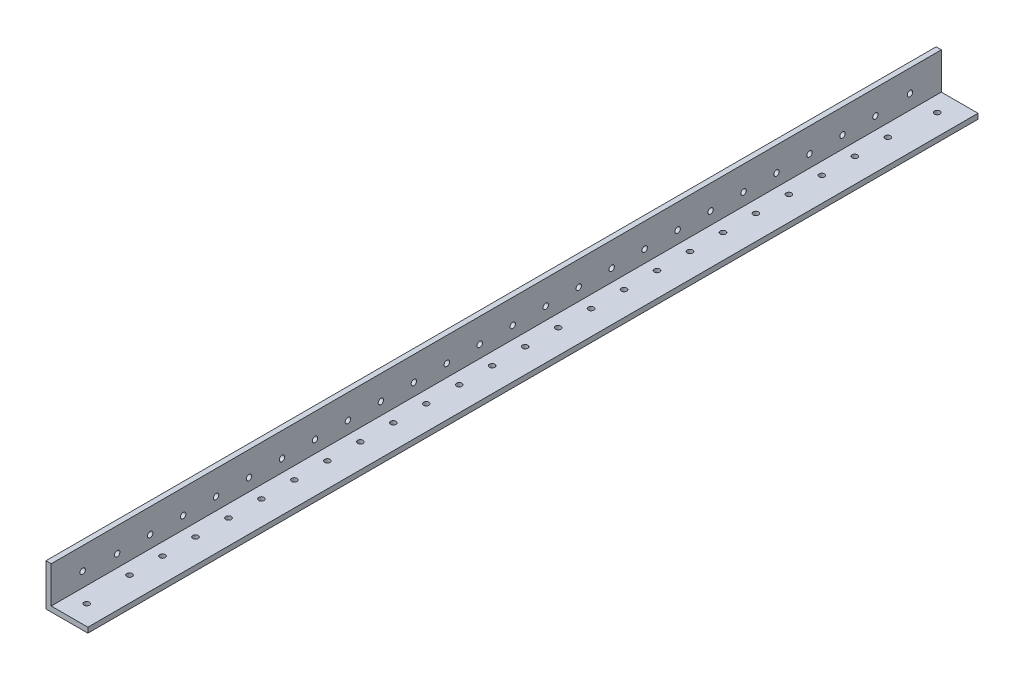
SolidWorks part; units mm, degrees
ref_plane "Front Plane" through (0, 0, 0) normal (0, 0, 1) x (1, 0, 0)
ref_plane "Top Plane" through (0, 0, 0) normal (0, 1, 0) x (1, 0, 0)
ref_plane "Right Plane" through (0, 0, 0) normal (1, 0, 0) x (0, 0, -1)
sketch "Sketch1" plane through (0, 0, 0) normal (0, 0, 1) x (1, 0, 0)
  line L0 (0, 25.4) -> (0, 0) construction
  line L1 (0, 0) -> (25.4, 0) construction
  line L2 (25.4, 0) -> (25.4, 3.175) construction
  line L3 (25.4, 3.175) -> (3.175, 3.175) construction
  line L4 (3.175, 3.175) -> (3.175, 25.4) construction
  line L6 (3.175, 25.4) -> (0, 25.4) construction
  arc A0 (3.175, 3.5814) -> (3.5814, 3.175) centre (3.5814, 3.5814) ccw construction
  point P4 (0, 0)
  dimension "Inside Corner Radius" = 0.4064
  dimension "Outside Height" = 25.4
  dimension "Inside Height" = 22.225
  dimension "Outside Width" = 25.4
  dimension "Inside Width" = 22.225
  dimension "Wall Thickness" = 3.175
  dimension "Shape" = 90
sketch "Sketch2" plane through (0, 0, 0) normal (1, 0, 0) x (0, 0, -1)
  line L0 (1219.2, 0) -> (-1219.2, 0) construction
  line L1 (-1219.2, 25.4) -> (-1219.2, 0) construction
  line L2 (1219.2, 25.4) -> (1219.2, 0) construction
  point P0 (-1189.99, 0)
  point P4 (0, 0)
  point P6 (1189.99, 0)
  dimension "D1" = 29.21
  dimension "D2" = 29.21
  dimension "D3" = 25.4
  dimension "Length" = 2438.4
sketch "Sketch3" plane through (0, 0, 0) normal (0, 0, 1) x (1, 0, 0)
  line L0 (3.175, 25.4) -> (0, 25.4)
  line L1 (0, 25.4) -> (0, 0)
  line L2 (0, 0) -> (25.4, 0)
  line L3 (25.4, 0) -> (25.4, 3.175)
  line L4 (25.4, 3.175) -> (3.175, 3.175)
  line L5 (3.175, 3.175) -> (3.175, 25.4)
extrude "Boss-Extrude1" add sketch "Sketch3" along normal mid plane 2438.4
fillet "Fillet1" radius 0.4064 1 edges at (3.175, 3.175, 0)
sketch "Sketch4" plane through (0, 0, 0) normal (-1, 0, 0) x (0, 0, 1)
  line L0 (1219.2, 25.4) -> (1219.2, 0) construction
  line L1 (-1219.2, 25.4) -> (679.2, 25.4)
  line L2 (-1219.2, 25.4) -> (-1219.2, -77.8785)
  line L3 (-1219.2, -77.8785) -> (679.2, -77.8785)
  line L4 (679.2, 25.4) -> (679.2, -77.8785)
  dimension "D1" = 540
extrude "Cut-Extrude1" cut sketch "Sketch4" against normal blind 60
sketch "Sketch5" plane through (0, 0, 679.2) normal (0, 0, -1) x (-1, 0, 0)
  line L0 (-3.175, 3.5814) -> (-3.175, 25.4) construction
  line L1 (-3.175, 6.1219) -> (-5.652, 6.1219)
  line L2 (-3.175, 6.1219) -> (-3.175, 3.175)
  line L3 (-3.175, 3.175) -> (-5.652, 3.175)
  line L4 (-5.652, 6.1219) -> (-5.652, 3.175)
  line L5 (-25.4, 3.175) -> (-3.5814, 3.175) construction
extrude "Cut-Extrude2" cut sketch "Sketch5" against normal blind 600
sketch "Sketch8" plane through (3.175, 0, 0) normal (1, 0, 0) x (0, 0, -1)
  line L0 (-1219.2, 3.175) -> (-1219.2, 25.4) construction
  line L1 (-1219.2, 3.175) -> (-679.2, 3.175) construction
  line L2 (-679.2, 3.175) -> (-679.2, 25.4) construction
  circle A0 centre (-1179.2, 10.675) radius 1.65
  circle A1 centre (-1159.2, 10.675) radius 1.65
  circle A2 centre (-1139.2, 10.675) radius 1.65
  circle A3 centre (-1119.2, 10.675) radius 1.65
  circle A4 centre (-1099.2, 10.675) radius 1.65
  circle A5 centre (-1079.2, 10.675) radius 1.65
  circle A6 centre (-1059.2, 10.675) radius 1.65
  circle A7 centre (-1039.2, 10.675) radius 1.65
  circle A8 centre (-1019.2, 10.675) radius 1.65
  circle A9 centre (-999.2, 10.675) radius 1.65
  circle A10 centre (-979.2, 10.675) radius 1.65
  circle A11 centre (-959.2, 10.675) radius 1.65
  circle A12 centre (-939.2, 10.675) radius 1.65
  circle A13 centre (-919.2, 10.675) radius 1.65
  circle A14 centre (-899.2, 10.675) radius 1.65
  circle A15 centre (-879.2, 10.675) radius 1.65
  circle A16 centre (-859.2, 10.675) radius 1.65
  circle A17 centre (-839.2, 10.675) radius 1.65
  circle A18 centre (-819.2, 10.675) radius 1.65
  circle A19 centre (-799.2, 10.675) radius 1.65
  circle A20 centre (-779.2, 10.675) radius 1.65
  circle A21 centre (-759.2, 10.675) radius 1.65
  circle A22 centre (-739.2, 10.675) radius 1.65
  circle A23 centre (-719.2, 10.675) radius 1.65
  dimension "D1" = 40
  dimension "D2" = 3.3
  dimension "D3" = 7.5
  dimension "D5" = 40
  dimension "D4" = 24
extrude "Cut-Extrude4" cut sketch "Sketch8" against normal blind 20
sketch "Sketch9" plane through (0, 3.175, 0) normal (0, 1, 0) x (1, 0, 0)
  line L0 (25.4, -1219.2) -> (3.175, -1219.2) construction
  line L1 (3.175, -1219.2) -> (3.175, -679.2) construction
  line L2 (25.4, -679.2) -> (3.175, -679.2) construction
  circle A0 centre (10.675, -1179.2) radius 1.65
  circle A1 centre (10.675, -1159.2) radius 1.65
  circle A2 centre (10.675, -1139.2) radius 1.65
  circle A3 centre (10.675, -1119.2) radius 1.65
  circle A4 centre (10.675, -1099.2) radius 1.65
  circle A5 centre (10.675, -1079.2) radius 1.65
  circle A6 centre (10.675, -1059.2) radius 1.65
  circle A7 centre (10.675, -1039.2) radius 1.65
  circle A8 centre (10.675, -1019.2) radius 1.65
  circle A9 centre (10.675, -999.2) radius 1.65
  circle A10 centre (10.675, -979.2) radius 1.65
  circle A11 centre (10.675, -959.2) radius 1.65
  circle A12 centre (10.675, -939.2) radius 1.65
  circle A13 centre (10.675, -919.2) radius 1.65
  circle A14 centre (10.675, -899.2) radius 1.65
  circle A15 centre (10.675, -879.2) radius 1.65
  circle A16 centre (10.675, -859.2) radius 1.65
  circle A17 centre (10.675, -839.2) radius 1.65
  circle A18 centre (10.675, -819.2) radius 1.65
  circle A19 centre (10.675, -799.2) radius 1.65
  circle A20 centre (10.675, -779.2) radius 1.65
  circle A21 centre (10.675, -759.2) radius 1.65
  circle A22 centre (10.675, -739.2) radius 1.65
  circle A23 centre (10.675, -719.2) radius 1.65
  dimension "D1" = 40
  dimension "D2" = 3.3
  dimension "D3" = 7.5
  dimension "D4" = 24
  dimension "D5" = 40
extrude "Cut-Extrude5" cut sketch "Sketch9" against normal blind 20
sketch "Sketch10" plane through (3.175, 0, 0) normal (1, 0, 0) x (0, 0, -1)
  circle A0 centre (-1200.15, 11.9634) radius 1.65
  circle A1 centre (-698.25, 11.9634) radius 1.65
  dimension "D1" = 3.3
extrude "Cut-Extrude6" cut sketch "Sketch10" against normal blind 70
sketch "Sketch11" plane through (0, 3.175, 0) normal (0, 1, 0) x (1, 0, 0)
  circle A0 centre (12.7, -691.1957) radius 1.65
  circle A1 centre (12.7, -1207.2043) radius 1.65
  dimension "D1" = 3.3
extrude "Cut-Extrude7" cut sketch "Sketch11" against normal blind 70
equation "\"D1@Boss-Extrude1\"=\"Length@Sketch2\""
equation "\"D1@Sketch2\" = \"Outside Width@Sketch1\" * 1.15"
equation "\"D2@Sketch2\"=\"D1@Sketch2\""
equation "\"D1@Fillet1\"=\"Inside Corner Radius@Sketch1\""
equation "\"D3@Sketch2\"=\"Outside Height@Sketch1\""
